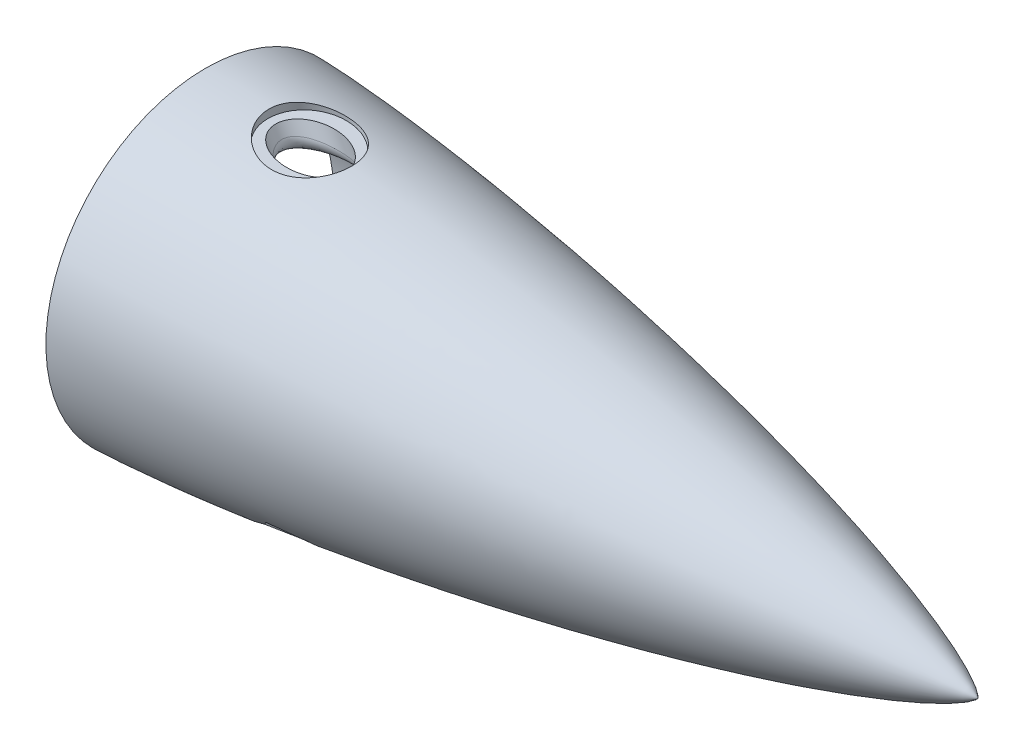
SolidWorks part; units mm, degrees
material "ABS"
ref_plane "Front Plane" through (0, 0, 0) normal (0, 0, 1) x (1, 0, 0)
ref_plane "Top Plane" through (0, 0, 0) normal (0, 1, 0) x (1, 0, 0)
ref_plane "Right Plane" through (0, 0, 0) normal (1, 0, 0) x (0, 0, -1)
ref_axis "Axis1" through (444.767, 0, 0) along (-1, 0, 0)
sketch "Sketch10" plane through (0, 0, 0) normal (0, 0, 1) x (1, 0, 0)
  line L1 (-0.5188, 0) -> (486.9547, 0) construction
  line L2 (3.3953, 69.55) -> (3.3953, 64.55)
  line L3 (3.3953, 69.55) -> (0.3953, 69.55)
  line L4 (409.4812, 0) -> (389.4812, 0)
  line L7 (0.3953, 69.55) -> (0.3953, 84.55)
  line L8 (3.3953, 64.55) -> (121.5873, 64.55)
  line L9 (444.767, 0) -> (-98.162, 0) construction
  spline S0 degree 4 poles (409.4812, 0) (409.4788, 0.0135) (409.4718, 0.0399) (409.45, 0.0903) (409.4052, 0.1736) (409.3386, 0.2747) (409.2332, 0.4144) (409.0715, 0.6026) (408.8144, 0.8684) (408.376, 1.2687) (407.6237, 1.874) (406.3009, 2.8069) (403.9508, 4.2541) (399.8003, 6.4739) (392.937, 9.6599) (381.0889, 14.4581) (364.0279, 20.4397) (342.5658, 27.076) (317.7374, 33.9485) (292.1491, 40.4025) (266.444, 46.3727) (240.6453, 51.9227) (214.7673, 57.0897) (188.82, 61.8964) (166.0615, 65.7958) (146.5183, 68.9193) (130.2092, 71.3728) (117.1484, 73.2437) (104.0744, 75.0198) (92.6232, 76.4872) (82.7998, 77.6794) (74.6082, 78.627) (68.0516, 79.3563) (61.4918, 80.0556) (54.9286, 80.7233) (48.3622, 81.3575) (41.7923, 81.956) (36.0408, 82.4459) (31.1087, 82.8394) (26.9972, 83.1482) (23.7071, 83.3831) (20.0917, 83.6266) (16.7244, 83.837) (13.6055, 84.0163) (10.7352, 84.1667) (8.4384, 84.2771) (6.1411, 84.3768) (4.1305, 84.4519) (2.4068, 84.5068) (1.2575, 84.5344) (0.6827, 84.5468) (0.3953, 84.55) knots 0 0 0 0 0 0.00013 0.00026 0.00052 0.0009 0.00128 0.001925 0.002882 0.004418 0.006927 0.011111 0.018279 0.030673 0.051704 0.083102 0.139909 0.202703 0.265496 0.32829 0.391083 0.453877 0.516671 0.579464 0.642258 0.673655 0.705051 0.736448 0.767845 0.799242 0.81494 0.830639 0.846337 0.862036 0.877734 0.893432 0.909131 0.924829 0.932678 0.940527 0.948377 0.956226 0.967169 0.972641 0.978113 0.983585 0.989056 0.994528 0.997264 1 1 1 1 1 construction
  spline S1 degree 4 poles (409.4812, 0) (409.4788, 0.0135) (409.4718, 0.0399) (409.45, 0.0903) (409.4052, 0.1736) (409.3386, 0.2747) (409.2332, 0.4144) (409.0715, 0.6026) (408.8144, 0.8684) (408.376, 1.2687) (407.6237, 1.874) (406.3009, 2.8069) (403.9508, 4.2541) (399.8003, 6.4739) (392.937, 9.6599) (381.0889, 14.4581) (364.0279, 20.4397) (342.5658, 27.076) (317.7374, 33.9485) (292.1491, 40.4025) (266.444, 46.3727) (240.6453, 51.9227) (214.7673, 57.0897) (188.82, 61.8964) (166.0615, 65.7958) (146.5183, 68.9193) (130.2092, 71.3728) (117.1484, 73.2437) (104.0744, 75.0198) (92.6232, 76.4872) (82.7998, 77.6794) (74.6082, 78.627) (68.0516, 79.3563) (61.4918, 80.0556) (54.9286, 80.7233) (48.3622, 81.3575) (41.7923, 81.956) (36.0408, 82.4459) (31.1087, 82.8394) (26.9972, 83.1482) (23.7071, 83.3831) (20.0917, 83.6266) (16.7244, 83.837) (13.6055, 84.0163) (10.7352, 84.1667) (8.4384, 84.2771) (6.1411, 84.3768) (4.1305, 84.4519) (2.4068, 84.5068) (1.2575, 84.5344) (0.6827, 84.5468) (0.3953, 84.55) knots 0 0 0 0 0 0.00013 0.00026 0.00052 0.0009 0.00128 0.001925 0.002882 0.004418 0.006927 0.011111 0.018279 0.030673 0.051704 0.083102 0.139909 0.202703 0.265496 0.32829 0.391083 0.453877 0.516671 0.579464 0.642258 0.673655 0.705051 0.736448 0.767845 0.799242 0.81494 0.830639 0.846337 0.862036 0.877734 0.893432 0.909131 0.924829 0.932678 0.940527 0.948377 0.956226 0.967169 0.972641 0.978113 0.983585 0.989056 0.994528 0.997264 1 1 1 1 1
  spline S2 degree 4 poles (389.4812, 0) (389.479, 0.0123) (389.4724, 0.0363) (389.4524, 0.0822) (389.412, 0.1569) (389.3528, 0.2469) (389.2596, 0.3707) (389.116, 0.5387) (388.8856, 0.7778) (388.4915, 1.1386) (387.8126, 1.6854) (386.6208, 2.5252) (384.5016, 3.8269) (380.7799, 5.8078) (374.6778, 8.6215) (364.2011, 12.8293) (349.1637, 18.0457) (330.2743, 23.8076) (308.4217, 29.7544) (285.9004, 35.3204) (263.2763, 40.4518) (240.5702, 45.2052) (217.7948, 49.6139) (194.959, 53.6981) (174.9303, 56.9957) (157.7317, 59.6247) (143.3798, 61.6809) (131.8866, 63.2429) (120.3822, 64.7193) (110.3061, 65.9329) (101.6625, 66.9139) (94.4549, 67.6898) (88.6861, 68.2846) (82.9146, 68.8522) (77.1403, 69.3912) (71.3632, 69.9) (65.5834, 70.3763) (60.5237, 70.7625) (56.185, 71.0696) (52.5683, 71.3081) (49.6742, 71.4878) (46.5171, 71.6708) (43.0969, 71.8518) (39.9065, 72.0008) (36.946, 72.119) (34.4784, 72.2017) (32.7508, 72.2492) (31.2698, 72.2816) (30.2823, 72.2953) (29.7885, 72.301) (29.5416, 72.3012) knots 0 0 0 0 0 0.000135 0.00027 0.00054 0.00092 0.001299 0.001947 0.002931 0.004512 0.007081 0.01138 0.018708 0.031424 0.052705 0.084103 0.14091 0.203703 0.266497 0.329291 0.392084 0.454878 0.517672 0.580465 0.643259 0.674656 0.706052 0.737449 0.768846 0.800243 0.815941 0.831639 0.847338 0.863036 0.878735 0.894433 0.910132 0.92583 0.933679 0.941528 0.949378 0.957227 0.96792 0.978613 0.98396 0.989307 0.994653 0.997327 1 1 1 1 1 construction
  spline S3 degree 4 poles (389.4812, 0) (389.479, 0.0123) (389.4724, 0.0363) (389.4524, 0.0822) (389.412, 0.1569) (389.3528, 0.2469) (389.2596, 0.3707) (389.116, 0.5387) (388.8856, 0.7778) (388.4915, 1.1386) (387.8126, 1.6854) (386.6208, 2.5252) (384.5016, 3.8269) (380.7799, 5.8078) (374.6778, 8.6215) (364.2011, 12.8293) (349.1637, 18.0457) (330.2743, 23.8076) (308.4217, 29.7544) (285.9004, 35.3204) (263.2763, 40.4518) (240.5702, 45.2052) (217.7948, 49.6139) (194.959, 53.6981) (174.9303, 56.9957) (157.7317, 59.6247) (143.3798, 61.6809) (133.6247, 63.0067) (126.7375, 63.9011) (122.7241, 64.4077) (121.5873, 64.55) knots 0 0 0 0 0 0.000135 0.00027 0.00054 0.00092 0.001299 0.001947 0.002931 0.004512 0.007081 0.01138 0.018708 0.031424 0.052705 0.084103 0.14091 0.203703 0.266497 0.329291 0.392084 0.454878 0.517672 0.580465 0.643259 0.674656 0.706052 0.737449 0.749854 0.749854 0.749854 0.749854 0.749854
  dimension "D1" = 84.55
  dimension "D3" = 410
  dimension "D5" = 390
  dimension "D7" = 20
  dimension "D8" = 118.192
  dimension "D2" = 15
  dimension "D4" = 3
revolve "Revolve1" add sketch "Sketch10" angle 360 about axis through (444.767, 0, 0) along (-1, 0, 0)
ref_plane "Plane3" through (0, 82.55, 0) normal (0, 1, 0) x (1, 0, 0)
sketch "Sketch20" plane through (0, 82.55, 0) normal (0, 1, 0) x (1, 0, 0)
  line L0 (444.767, 0) -> (-98.162, 0) construction
  line L1 (24.7702, 25) -> (64.7702, 25)
  line L2 (24.7702, 25) -> (24.7702, -15)
  line L3 (24.7702, -15) -> (64.7702, -15)
  line L4 (64.7702, 25) -> (64.7702, -15)
  line L5 (24.7702, 25) -> (64.7702, -15) construction
  line L6 (24.7702, -15) -> (64.7702, 25) construction
  point P4 (44.7702, 5)
  dimension "D1" = 40
  dimension "D2" = 15
  dimension "D3" = 40
extrude "Cut-Extrude3" [suppressed] cut sketch "Sketch20" along normal blind 12
sketch "Sketch22" plane through (0, 82.55, 0) normal (0, 1, 0) x (1, 0, 0)
  circle A0 centre (32, 6) radius 7.5
  dimension "D1" = 15
extrude "Cut-Extrude4" [suppressed] cut sketch "Sketch22" along normal through all
sketch "Sketch24" plane through (0, 82.55, 0) normal (0, 1, 0) x (1, 0, 0)
  line L0 (38.1988, 66.2764) -> (38.1988, 16.8548) construction
ref_plane "Plane4" through (-26.1955, 45.3719, 0) normal (-0.5, 0.866, 0) x (0, 0, 1)
sketch "Sketch26" plane through (-26.1955, 45.3719, 0) normal (-0.5, 0.866, 0) x (0, 0, 1)
  line L1 (-66.2764, 74.3561) -> (-16.8548, 74.3561) construction
  circle A0 centre (0, 86.3561) radius 15
  dimension "D1" = 12
extrude "Cut-Extrude5" cut sketch "Sketch26" against normal blind 50
ref_plane "Plane5" through (8.9989, 85.619, 0) normal (0.1045, 0.9945, 0) x (0, 0, 1)
sketch "Sketch30" plane through (8.9989, 85.619, 0) normal (0.1045, 0.9945, 0) x (0, 0, 1)
  line L0 (0, 442.3305) -> (0, -97.6242) construction
  circle A0 centre (0, 47.1511) radius 22
extrude "Cut-Extrude10" cut sketch "Sketch30" against normal blind 5
fillet "Fillet1" radius 5 1 edges at (79.2639, 64.4372, 3.8138)
hole_wizard "Tap Drill for 1/4 Helicoil1" positions "Sketch31" profile "Sketch32" hole size "1/4-20" standard "ANSI Inch"
sketch "Sketch31" plane through (0.3953, 0, 0) normal (-1, 0, 0) x (0, 0, 1)
  line L1 (0, 0) -> (0, 69.55)
  circle A1 centre (0, 0) radius 69.55
  circle A2 centre (0, 0) radius 84.55 construction
  point P0 (-220.8452, 298.3381)
  point P23 (0, 69.55)
  dimension "D1" = 15
sketch "Sketch32" plane through (0.3953, 298.3381, -220.8452) normal (0, 1, 0) x (0, 0, 1)
  line L0 (0, 0) -> (0, 20)
  line L1 (0, 20) -> (3.3782, 20)
  line L2 (3.3782, 20) -> (3.3782, 0)
  line L5 (3.3782, 0) -> (0, 0)
  line L10 (0, 20) -> (-3.3782, 20) construction
  line L11 (0, -6.35) -> (0, 107.95) construction
  dimension "Hole Dia." = 6.7564
  dimension "Hole Depth" = 20
  dimension "Drill Angle" = 180
pattern_circular "CirPattern1" count 6 over 360 about axis through (444.767, 0, 0) along (-1, 0, 0) of "Tap Drill for 1/4 Helicoil1"
equation "\"TubeDiameter\" = 6.500in"
equation "\"D1@Sketch10\"=\"TubeDiameter\"/2mm+2mm"
equation "\"D1@Plane3\"=\"TubeDiameter\"/2mm"
